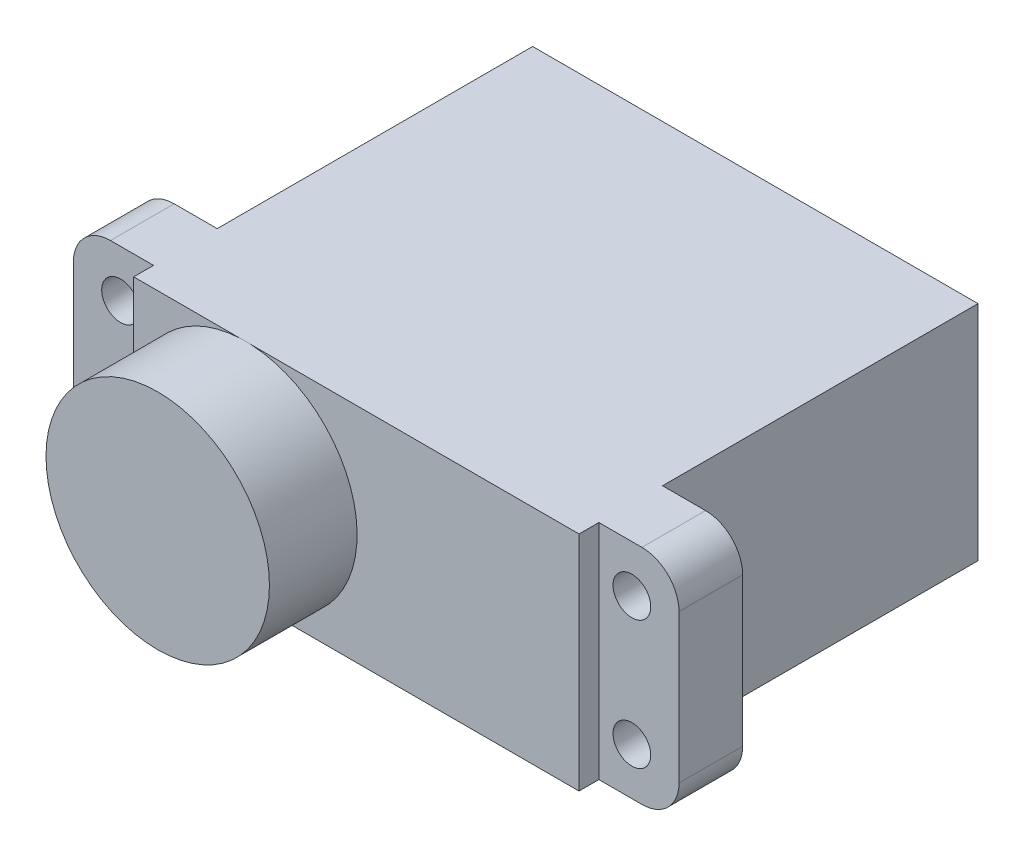
SolidWorks part; units mm, degrees
note: '?' marks a value the reader was unsure of.
ref_plane "Front Plane" through (0, 0, 0) normal (0, 0, 1) x (1, 0, 0)
ref_plane "Top Plane" through (0, 0, 0) normal (0, 1, 0) x (1, 0, 0)
ref_plane "Right Plane" through (0, 0, 0) normal (1, 0, 0) x (0, 0, -1)
sketch "Sketch1" plane through (0, 0, 0) normal (0, 0, 1) x (1, 0, 0)
  line L1 (0, 12) -> (-24, 12)
  line L2 (0, 12) -> (0, 0)
  line L3 (0, 0) -> (-24, 0)
  line L4 (-24, 12) -> (-24, 0)
  dimension "D1" = 24
  dimension "D2" = 12
extrude "Extrude1" add sketch "Sketch1" along normal blind 21.5
sketch "Sketch2" plane through (-24, 0, 0) normal (-1, 0, 0) x (0, 0, 1)
  line L0 (21.5, 12) -> (0, 12) construction
  line L1 (20.43, 12) -> (17, 12)
  line L2 (20.43, 12) -> (20.43, 0)
  line L3 (20.43, 0) -> (17, 0)
  line L4 (17, 12) -> (17, 0)
  line L5 (21.5, 0) -> (0, 0) construction
  dimension "D1" = 17
  dimension "D2" = 3.43
extrude "Extrude2" add sketch "Sketch2" along normal blind 4.318
fillet "Fillet1" radius 2 3 edges at (-28.318, 12, 18.715)
fillet "Fillet2" radius 2 3 edges at (-28.318, 0, 18.715)
ref_point "Point1"
ref_axis "Axis1" through (-12, 49.046, 21.5) along (0, -1, 0)?
ref_plane "Plane1" through (-12, 0, 0) normal (-1, 0, 0) x (0, 0, 1)
sketch "Sketch3" plane through (0, 0, 20.43) normal (0, 0, 1) x (1, 0, 0)
  line L0 (-26.318, 12) -> (-24, 12) construction
  line L1 (-24, 0) -> (-24, 12) construction
  line L2 (-26.318, 0) -> (-24, 0) construction
  circle A0 centre (-25.778, 2.5362) radius 1.016
  circle A1 centre (-25.778, 9.46) radius 1.016
  dimension "D5" = 2.032
  dimension "D1" = 2.54
  dimension "D2" = 1.778
  dimension "D3" = 2.5362
  dimension "D4" = 1.778
extrude "Cut-Extrude1" cut sketch "Sketch3" against normal blind 4.318
mirror "Mirror1" about plane through (-12, 0, 0) normal (-1, 0, 0) of "Cut-Extrude1", "Fillet2", "Fillet1", "Extrude2"
sketch "Sketch4" plane through (0, 0, 21.5) normal (0, 0, 1) x (1, 0, 0)
  line L0 (-24, 12) -> (-24, 0) construction
  circle A0 centre (-17.98, 5.9871) radius 6.02
extrude "Extrude3" add sketch "Sketch4" along normal blind 4.725
